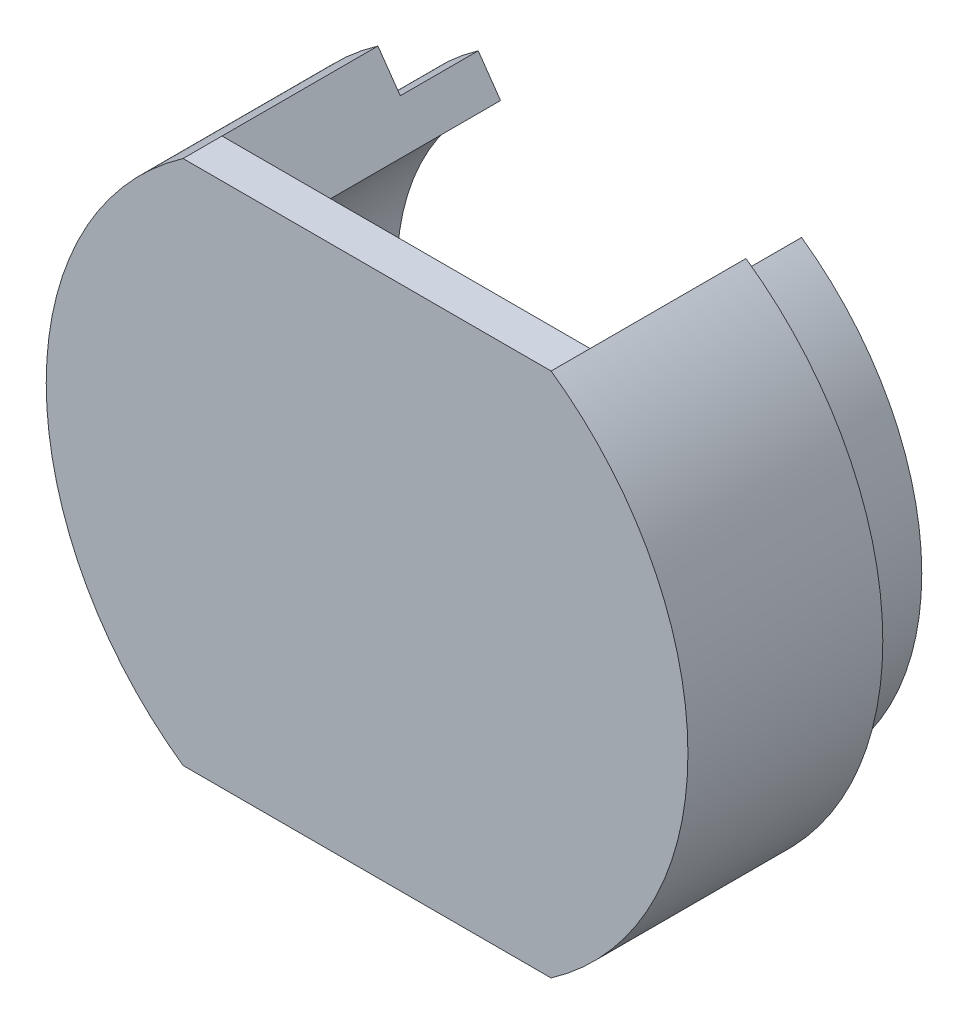
SolidWorks part; units mm, degrees
ref_plane "Front Plane" through (0, 0, 0) normal (0, 0, 1) x (1, 0, 0)
ref_plane "Top Plane" through (0, 0, 0) normal (0, 1, 0) x (1, 0, 0)
ref_plane "Right Plane" through (0, 0, 0) normal (1, 0, 0) x (0, 0, -1)
sketch "Sketch1" plane through (0, 0, 0) normal (0, 0, 1) x (1, 0, 0)
  line L0 (0, 31.1622) -> (0, 36.1622) construction
  circle A0 centre (0, 0) radius 36.1622
  circle A1 centre (0, 0) radius 31.1622
  dimension "D1" = 72.3245
  dimension "D2" = 5
extrude "Boss-Extrude1" add sketch "Sketch1" along normal mid plane 10
sketch "Sketch2" plane through (0, 0, 0) normal (0, 0, 1) x (1, 0, 0)
  line L0 (0, 0) -> (-20.7418, 29.6224) construction
  line L1 (0, 0) -> (0, 36.1622) construction
  line L2 (0, 0) -> (20.7418, 29.6224) construction
  line L3 (20.7418, 29.6224) -> (17.8739, 25.5266)
  line L4 (-17.8739, 25.5266) -> (-20.7418, 29.6224)
  circle A0 centre (0, 0) radius 36.1622 construction
  arc A1 (-17.8739, 25.5266) -> (17.8739, 25.5266) centre (0, 0) cw
  circle A2 centre (0, 0) radius 31.1622 construction
  arc A3 (-20.7418, 29.6224) -> (20.7418, 29.6224) centre (0, 0) cw
  dimension "D1" = 70
extrude "Cut-Extrude1" cut sketch "Sketch2" against normal through all both and the other way through all
mirror "Mirror1" about plane through (0, 0, 0) normal (0, 1, 0) of "Cut-Extrude1"
sketch "Sketch3" plane through (0, 0, 5) normal (0, 0, 1) x (1, 0, 0)
  line L0 (-17.8739, 25.5266) -> (-23.6097, 33.7181)
  line L1 (-17.8739, -25.5266) -> (-23.6097, -33.7181)
  line L2 (-20.7418, 29.6224) -> (-17.8739, 25.5266) construction
  line L3 (-20.7418, -29.6224) -> (-17.8739, -25.5266) construction
  line L4 (0, 0) -> (0, 25.5266) construction
  line L5 (17.8739, -25.5266) -> (23.6097, -33.7181)
  line L6 (17.8739, 25.5266) -> (23.6097, 33.7181)
  arc A0 (-17.8739, 25.5266) -> (-17.8739, -25.5266) centre (0, 0) ccw construction
  arc A1 (-17.8739, 25.5266) -> (-17.8739, -25.5266) centre (0, 0) ccw
  arc A2 (-23.6097, -33.7181) -> (-23.6097, 33.7181) centre (0, 0) cw
  arc A3 (23.6097, -33.7181) -> (23.6097, 33.7181) centre (0, 0) ccw
  arc A4 (17.8739, 25.5266) -> (17.8739, -25.5266) centre (0, 0) cw
  point P10 (0, 0)
  dimension "D1" = 10
extrude "Boss-Extrude2" add sketch "Sketch3" along normal blind 20
sketch "Sketch4" plane through (0, 0, 25) normal (0, 0, 1) x (1, 0, 0)
  line L0 (23.6097, 33.7181) -> (-23.6097, 33.7181)
  line L1 (23.6097, -33.7181) -> (-23.6097, -33.7181)
  circle A0 centre (0, 0) radius 41.1622 construction
  arc A1 (23.6097, -33.7181) -> (23.6097, 33.7181) centre (0, 0) ccw construction
  arc A2 (-23.6097, -33.7181) -> (-23.6097, 33.7181) centre (0, 0) cw
  arc A3 (23.6097, 33.7181) -> (23.6097, -33.7181) centre (0, 0) cw
extrude "Boss-Extrude3" add sketch "Sketch4" along normal blind 5
